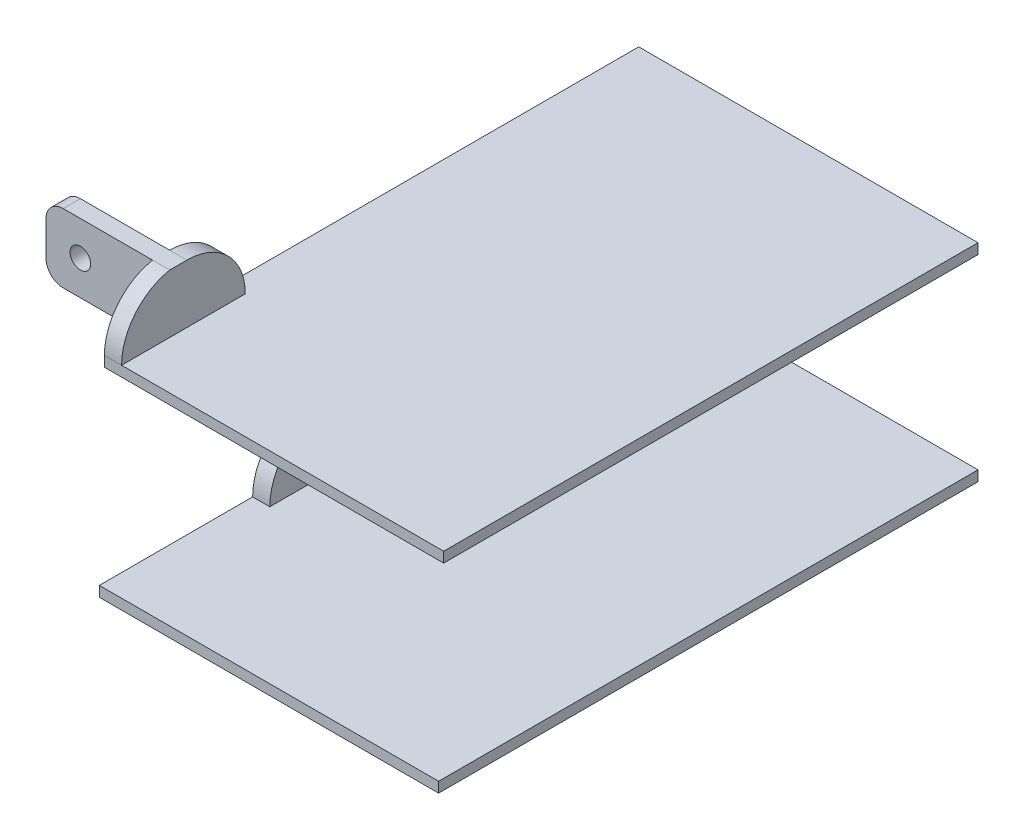
SolidWorks part; units mm, degrees
ref_plane "Front Plane" through (0, 0, 0) normal (0, 0, 1) x (1, 0, 0)
ref_plane "Top Plane" through (0, 0, 0) normal (0, 1, 0) x (1, 0, 0)
ref_plane "Right Plane" through (0, 0, 0) normal (1, 0, 0) x (0, 0, -1)
sketch "Sketch3" plane through (0, 0, 0) normal (0, 0, 1) x (1, 0, 0)
  line L0 (-76.2993, 0) -> (18.6887, 0)
ref_plane "Lower tab plane" through (0, 0, 0) normal (0, 0.1736, 0.9848) x (1, 0, 0)
sketch "Sketch1" plane through (0, 0, 0) normal (0, 0.1736, 0.9848) x (1, 0, 0)
  line L1 (-124.75, 10) -> (-93.75, 10)
  line L2 (-129.75, 5) -> (-129.75, -5)
  line L3 (-124.75, -10) -> (-93.75, -10)
  line L4 (-93.75, 10) -> (-93.75, -10)
  circle A0 centre (-119.75, 0) radius 3
  circle A1 centre (-105.25, 0) radius 3
  arc A2 (-129.75, -5) -> (-124.75, -10) centre (-124.75, -5) ccw
  arc A3 (-124.75, 10) -> (-129.75, 5) centre (-124.75, 5) ccw
  point P4 (-93.75, 0)
  point P8 (-128.1754, -10)
  point P11 (0, 0)
  point P12 (-119.75, 0)
  point P13 (-105.8098, -0.9456)
  point P18 (-129.75, 10)
  dimension "D4" = 6
  dimension "D5" = 6
  dimension "D8" = 5
  dimension "D1" = 36
  dimension "D2" = 20
  dimension "D3" = 119.75
  dimension "D6" = 14.5
  dimension "D7" = 10
extrude "Lower left tab" add sketch "Sketch1" along normal blind 5
sketch "Sketch2" plane through (-93.75, 0, 0) normal (1, 0, 0) x (0, 0, -1)
  line L1 (-68.7365, -6.8481) -> (88.2635, -6.8481)
  line L2 (-68.7365, -6.8481) -> (-68.7365, -9.8481)
  line L3 (-68.7365, -9.8481) -> (88.2635, -9.8481)
  line L4 (88.2635, -6.8481) -> (88.2635, -9.8481)
  dimension "D1" = 3
  dimension "D2" = 90
  dimension "D3" = 67
extrude "Bottom plate extrude" add sketch "Sketch2" along normal blind 93.75 and the other way blind 5
sketch "Sketch4" plane through (-93.75, 0, 0) normal (1, 0, 0) x (0, 0, -1)
  line L0 (88.2635, -6.8481) -> (-68.7365, -6.8481) construction
  line L1 (15.7462, -6.8481) -> (-1.2075, -6.8481)
  line L2 (-6.2846, -6.8481) -> (-3.1876, 10.7163) construction
  line L3 (-1.2075, -6.8481) -> (1.7365, 9.8481) construction
  line L4 (-6.2846, -6.8481) -> (-3.1876, 10.7163)
  line L5 (-1.2075, -6.8481) -> (1.7365, 9.8481)
  line L6 (-6.2846, -6.8481) -> (-24.12, -6.8481)
  line L7 (-3.1876, 10.7163) -> (1.7365, 9.8481) construction
  arc A0 (1.7365, 9.8481) -> (15.7462, -6.8481) centre (-1.2075, -6.8481) cw
  arc A1 (-3.1876, 10.7163) -> (-24.12, -6.8481) centre (-6.2846, -6.8481) ccw
  point P10 (-26.5692, -6.8481)
  point P11 (0, 0)
  point P13 (0, 0)
  point P14 (0, 0)
extrude "Bottom tab support extrude" add sketch "Sketch4" against normal blind 5
ref_plane "Plane2" through (0, 0, -1.7365) normal (0, 0, 1) x (1, 0, 0)
ref_plane "Top tab plane" through (0, 0, 48.2635) normal (0, 0, 1) x (1, 0, 0)
sketch "Sketch5" plane through (0, 0, 48.2635) normal (0, 0, 1) x (1, 0, 0)
  line L0 (-129.75, 5.7923) -> (-129.75, -4.0558) construction
  line L1 (-124.75, 67.4019) -> (-93.75, 67.4019)
  line L2 (-129.75, 62.4019) -> (-129.75, 52.4019)
  line L3 (-124.75, 47.4019) -> (-93.75, 47.4019)
  line L4 (-93.75, 67.4019) -> (-93.75, 47.4019)
  line L5 (-93.75, -6.8481) -> (-93.75, 10.9873) construction
  arc A0 (-129.75, 52.4019) -> (-124.75, 47.4019) centre (-124.75, 52.4019) ccw
  arc A1 (-124.75, 67.4019) -> (-129.75, 62.4019) centre (-124.75, 62.4019) ccw
  circle A2 centre (-119.75, 57.4019) radius 3
  ellipse E0 centre (-119.75, 0.8682) end of major axis (-116.75, 0.8682) minor radius 2.9544 construction
  ellipse E1 centre (-119.75, 0.8682) end of major axis (-116.75, 0.8682) minor radius 2.9544 construction
  point P14 (0, 0)
  point P26 (0, 0)
  point P27 (0, 0)
  point P28 (-93.75, 57.4019)
  dimension "D2" = 5
  dimension "D3" = 6
  dimension "D1" = 20
  dimension "D4" = 67.25
extrude "Top tab extrude" add sketch "Sketch5" along normal blind 5 separate body
sketch "Sketch6" plane through (-93.75, 0, 0) normal (1, 0, 0) x (0, 0, -1)
  line L0 (-53.2635, 47.4019) -> (-48.2635, 47.4019) construction
  line L1 (-67.2635, 47.4019) -> (88.2635, 47.4019)
  line L2 (-67.2635, 47.4019) -> (-67.2635, 50.4019)
  line L3 (-67.2635, 50.4019) -> (88.2635, 50.4019)
  line L4 (88.2635, 47.4019) -> (88.2635, 50.4019)
  line L5 (-48.2635, 47.4019) -> (-48.2635, 67.4019) construction
  line L6 (88.2635, -9.8481) -> (88.2635, -6.8481) construction
  point P8 (0, 0)
  dimension "D1" = 3
  dimension "D2" = 19
extrude "Top plate extrude" add sketch "Sketch6" against normal blind 5 and the other way up to surface (93.75 mm away) other way up to face at (0, -8.3481, -9.7635)
sketch "Sketch7" plane through (-93.75, 0, 0) normal (1, 0, 0) x (0, 0, -1)
  line L0 (-48.2635, 50.4019) -> (-48.2635, 67.4019) construction
  line L1 (88.2635, 50.4019) -> (-67.2635, 50.4019) construction
  line L2 (-53.2635, 50.4019) -> (-53.2635, 67.4019) construction
  line L3 (-48.2635, 50.4019) -> (-48.2635, 67.4019)
  line L4 (-31.2635, 50.4019) -> (-48.2635, 50.4019)
  line L5 (-53.2635, 50.4019) -> (-53.2635, 67.4019)
  line L6 (-53.2635, 50.4019) -> (-67.2635, 50.4019)
  line L7 (-67.2635, 50.4019) -> (-67.2635, 47.4019) construction
  arc A0 (-67.2635, 50.4019) -> (-53.2635, 67.4019) centre (-49.9421, 50.4019) cw
  arc A1 (-48.2635, 67.4019) -> (-31.2635, 50.4019) centre (-48.2635, 50.4019) cw
  point P11 (0, 0)
extrude "Top tab support extrude" add sketch "Sketch7" against normal blind 5
